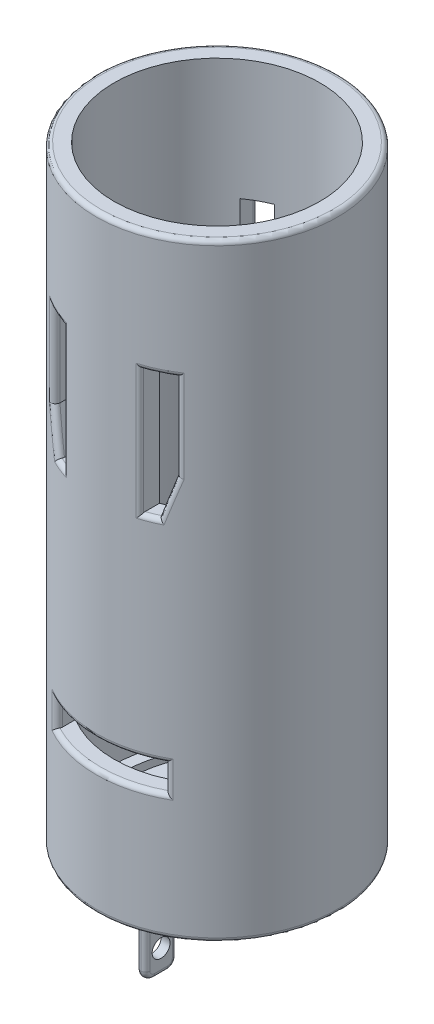
SolidWorks part; units mm, degrees
ref_plane "Front Plane" through (0, 0, 0) normal (0, 0, 1) x (1, 0, 0)
ref_plane "Top Plane" through (0, 0, 0) normal (0, 1, 0) x (1, 0, 0)
ref_plane "Right Plane" through (0, 0, 0) normal (1, 0, 0) x (0, 0, -1)
sketch "Sketch1" plane through (0, 0, 0) normal (0, 1, 0) x (1, 0, 0)
  circle A0 centre (0, 0) radius 13.5
  dimension "D1" = 27
extrude "Boss-Extrude1" add sketch "Sketch1" along normal blind 68
shell "Shell1" thickness 2 removed face at (0, 68, 13.5)
sketch "Sketch7" plane through (0, 0, 0) normal (1, 0, 0) x (0, 0, -1)
  line L0 (0, 38.9924) -> (0, -59.5447) construction
  line L1 (-6.75, 34.4901) -> (-6.75, -41.055) construction
  line L2 (6.75, 26.3233) -> (6.75, -38.8988) construction
  line L3 (-8.5, 0) -> (-5, 0)
  line L4 (-13.5, 0) -> (13.5, 0) construction
  line L5 (-5, 0) -> (-5, -8)
  line L6 (-6, -9) -> (-7.5, -9)
  line L7 (-8.5, -8) -> (-8.5, 0)
  line L8 (6, -9) -> (7.5, -9)
  line L9 (8.5, 0) -> (5, 0)
  line L10 (8.5, -8) -> (8.5, 0)
  line L11 (5, 0) -> (5, -8)
  arc A0 (-7.5, -9) -> (-8.5, -8) centre (-7.5, -8) cw
  arc A1 (-5, -8) -> (-6, -9) centre (-6, -8) cw
  circle A2 centre (-6.75, -6.3884) radius 1
  circle A3 centre (6.75, -6.3884) radius 1
  arc A4 (5, -8) -> (6, -9) centre (6, -8) ccw
  arc A5 (7.5, -9) -> (8.5, -8) centre (7.5, -8) ccw
  point P15 (-8.5, -9)
  point P18 (-5, -9)
  dimension "D4" = 1
  dimension "D5" = 1
  dimension "D6" = 2
  dimension "D1" = 6.75
  dimension "D2" = 6.75
  dimension "D3" = 3.5
  dimension "D7" = 8
extrude "Boss-Extrude5" add sketch "Sketch7" along normal mid plane 1
sketch "Sketch8" plane through (0, 0, 0) normal (0, -1, 0) x (1, 0, 0)
  circle A0 centre (0, 0) radius 1 construction
  circle A1 centre (0, 0) radius 3.5
  dimension "D1" = 2
  dimension "D2" = 7
extrude "Boss-Extrude6" add sketch "Sketch8" along normal blind 2
shell "Shell2" thickness 2 removed face at (0, -2, -3.5)
sketch "Sketch9" plane through (0, 0, 0) normal (0, -1, 0) x (1, 0, 0)
  circle A0 centre (0, 0) radius 1.5
  dimension "D1" = 3
extrude "Cut-Extrude1" cut sketch "Sketch9" against normal through all
sketch "Sketch10" plane through (0, 0, 0) normal (0, -1, 0) x (1, 0, 0)
  line L0 (-18.4289, 0) -> (18.8872, 0) construction
  line L1 (-14.2861, 6.6617) -> (17.8015, -8.301) construction
  line L2 (-15.4077, -7.1847) -> (15.5874, 7.2685) construction
  line L3 (0, 18.0607) -> (0, -19.4275) construction
  arc A0 (-9.2995, 4.3364) -> (-9.2995, -4.3364) centre (0, 0) ccw
  arc A1 (-8.3932, 3.9138) -> (-8.3932, -3.9138) centre (0, 0) ccw
  arc A2 (8.3932, -3.9138) -> (8.3932, 3.9138) centre (0, 0) ccw
  circle A3 centre (0, 0) radius 10.2608 construction
  circle A4 centre (0, 0) radius 9.2608 construction
  arc A5 (9.2995, -4.3364) -> (9.2995, 4.3364) centre (0, 0) ccw
  arc A6 (-8.3932, 3.9138) -> (-9.2995, 4.3364) centre (-8.8463, 4.1251) ccw
  arc A7 (-8.3932, -3.9138) -> (-9.2995, -4.3364) centre (-8.8463, -4.1251) cw
  arc A8 (8.3932, -3.9138) -> (9.2995, -4.3364) centre (8.8463, -4.1251) ccw
  arc A9 (8.3932, 3.9138) -> (9.2995, 4.3364) centre (8.8463, 4.1251) cw
  point P1 (9.2608, 0)
  point P11 (9.8125, 3)
  dimension "D2" = 25
  dimension "D1" = 1
extrude "Cut-Extrude2" cut sketch "Sketch10" against normal through all
fillet "Fillet3" radius 0.5 30 edges at (8.635, 0, 4.5783) (10.2608, 0, 0) (8.635, 0, -4.5783) (-8.635, 0, 4.5783) (-9.2608, 0, 0) (-8.635, 0, -4.5783) (-0.5, -4, 8.5) (-0.5, -8.7071, 8.2071) (-0.5, -9, 6.75) (-0.5, -8.7071, 5.2929) (-0.5, -4, -5) (-0.5, -8.7071, -5.2929) (-0.5, -9, -6.75) (-0.5, -8.7071, -8.2071) (0.5, -4, -5) (0.5, -8.7071, -5.2929) (0.5, -9, -6.75) (0.5, -8.7071, -8.2071) (0.5, -4, 8.5) (0.5, -8.7071, 8.2071) (0.5, -9, 6.75) (0.5, -8.7071, 5.2929) (9.2608, 0, 0) (-10.2608, 0, 0) (-0.5, -4, 5) (-0.5, -4, -8.5) (0.5, -4, -8.5) (0.5, -4, 5) (0, -2, -3.5) (0, 0, 13.5)
ref_plane "Plane1" through (0, 0, 13.5) normal (0, 0, 1) x (1, 0, 0)
sketch "Sketch11" plane through (0, 0, 13.5) normal (0, 0, 1) x (1, 0, 0)
  line L0 (0, 81.5719) -> (0, -34.7876) construction
  line L1 (-20.601, 15.5) -> (50.8297, 15.5) construction
  line L2 (13.5, 0.5) -> (-13.5, 0.5) construction
  line L3 (-6, 14) -> (-6, 17)
  line L4 (-6, 14) -> (6, 14)
  line L5 (-6, 17) -> (6, 17)
  line L6 (6, 14) -> (6, 17)
  dimension "D1" = 15
  dimension "D2" = 3
  dimension "D3" = 12
extrude "Cut-Extrude3" cut sketch "Sketch11" against normal through all both and the other way through all
fillet "Fillet4" radius 0.5 9 edges at (0, 68, 13.5) (0, 14, -13.5) (-6, 15.5, -12.0934) (0, 17, -13.5) (6, 15.5, -12.0934) (0, 17, 13.5) (-6, 15.5, 12.0934) (0, 14, 13.5) (6, 15.5, 12.0934)
sketch "Sketch12" plane through (0, 0, 0) normal (0, 0, 1) x (1, 0, 0)
  line L0 (0, 71.1248) -> (0, -13.4931) construction
  line L1 (-27.5431, 47.5) -> (38.0126, 47.5) construction
  line L2 (-13.5, 67.5) -> (13.5, 67.5) construction
  line L3 (-6.75, 64.1508) -> (-6.75, 25.4063) construction
  line L4 (6.75, 60.7413) -> (6.75, 23.5466) construction
  line L5 (6.75, 17.5) -> (6.75, 13.5) construction
  line L6 (-6.75, 13.5) -> (-6.75, 17.5) construction
  line L7 (-4.25, 54.5) -> (-4.25, 40.5)
  line L8 (-27.5431, 54.5) -> (35.6808, 54.5) construction
  line L9 (-26.6816, 40.5) -> (28.6035, 40.5) construction
  line L10 (-4.25, 54.5) -> (-6.75, 54.5)
  line L11 (-6.75, 54.5) -> (-6.75, 44.7786)
  line L12 (-6.75, 44.7786) -> (-5.5113, 40.5)
  line L13 (-5.5113, 40.5) -> (-4.25, 40.5)
  line L14 (5.5113, 40.5) -> (4.25, 40.5)
  line L15 (-4.25, 64.1508) -> (-4.25, 25.4063) construction
  line L16 (6.75, 44.7786) -> (5.5113, 40.5)
  line L17 (4.25, 54.5) -> (4.25, 40.5)
  line L18 (4.25, 54.5) -> (6.75, 54.5)
  line L19 (6.75, 54.5) -> (6.75, 44.7786)
  dimension "D1" = 20
  dimension "D3" = 7
  dimension "D4" = 7
  dimension "D2" = 2.5
extrude "Cut-Extrude4" cut sketch "Sketch12" against normal through all both and the other way through all
fillet "Fillet5" radius 0.5 10 edges at (5.5285, 54.5, 12.3161) (4.25, 47.5, 12.8136) (4.8868, 40.5, 12.5845) (6.1388, 42.6674, 12.0235) (6.75, 49.6393, 11.6913) (-6.1388, 42.6674, 12.0235) (-4.8868, 40.5, 12.5845) (-4.25, 47.5, 12.8136) (-5.5285, 54.5, 12.3161) (-6.75, 49.6393, 11.6913)
fillet "Fillet8" radius 0.5 10 edges at (6.75, 49.6393, -11.6913) (5.5285, 54.5, -12.3161) (6.1388, 42.6674, -12.0235) (4.8868, 40.5, -12.5845) (4.25, 47.5, -12.8136) (-6.1388, 42.6674, -12.0235) (-4.8868, 40.5, -12.5845) (-4.25, 47.5, -12.8136) (-6.75, 49.6393, -11.6913) (-5.5285, 54.5, -12.3161)
